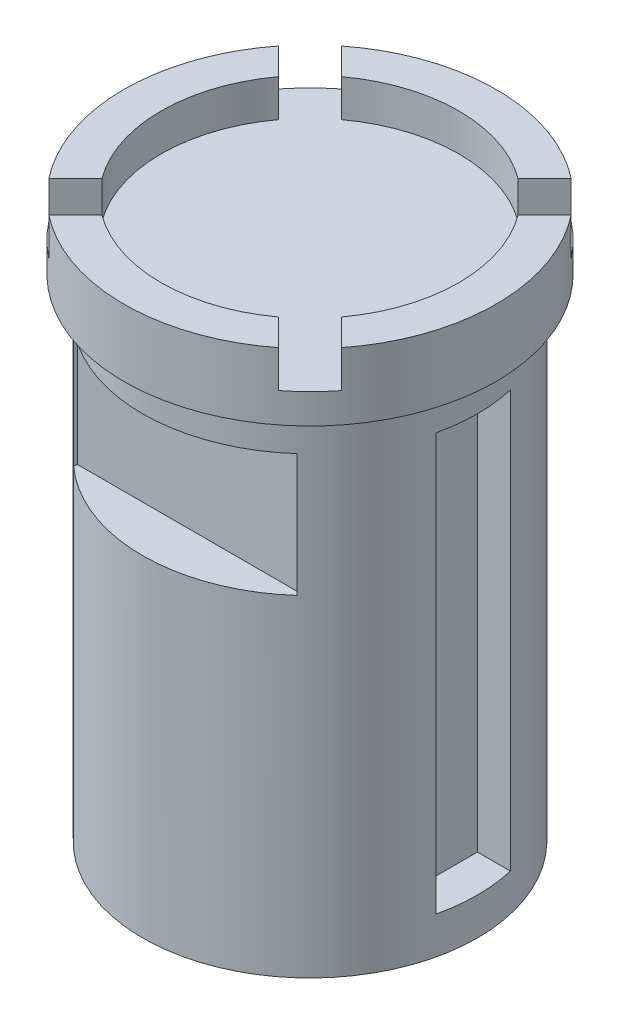
SolidWorks part; units mm, degrees
other "Satellite Body"
ref_plane "Front Plane" through (0, 0, 0) normal (0, 0, 1) x (1, 0, 0)
ref_plane "Top Plane" through (0, 0, 0) normal (0, 1, 0) x (1, 0, 0)
ref_plane "Right Plane" through (0, 0, 0) normal (1, 0, 0) x (0, 0, -1)
sketch "Body Block Sketch" plane through (0, 0, 0) normal (0, 0, 1) x (1, 0, 0)
  line L1 (0, 0) -> (400, 0)
  line L2 (0, 0) -> (0, -1400)
  line L3 (0, -1400) -> (450, -1400)
  line L6 (450, 0) -> (450, -80) construction
  line L9 (500, 0) -> (500, 100)
  line L13 (500, 100) -> (400, 100)
  line L14 (400, 0) -> (400, 100)
  line L15 (400, 0) -> (450, 0) construction
  line L16 (450, 0) -> (400, 0) construction
  line L17 (450, -80) -> (450, -1400)
  line L18 (450, -80) -> (500, -80)
  line L19 (500, 0) -> (500, -80)
  line L21 (400, 0) -> (500, 0) construction
  dimension "D1" = 1400
  dimension "D2" = 500
  dimension "D3" = 50
  dimension "D4" = 100
  dimension "D5" = 100
  dimension "D6" = 80
revolve "Body Block Revolve" add sketch "Body Block Sketch" angle 360 about L2
ref_plane "Surface Feature Start Plane" through (0, -180, 0) normal (0, -1, 0) x (-1, 0, 0)
sketch "Solar Divot Sketch" plane through (0, -180, 0) normal (0, -1, 0) x (-1, 0, 0)
  line L0 (0, 0) -> (-450, 0) construction
  line L1 (-450, 100) -> (-350, 100)
  line L2 (-450, 100) -> (-450, -100)
  line L3 (-450, -100) -> (-350, -100)
  line L4 (-350, 100) -> (-350, -100)
  line L5 (0, -926.423) -> (0, 49073.577) construction
  line L6 (350, 100) -> (350, -100)
  line L7 (450, -100) -> (350, -100)
  line L8 (450, 100) -> (450, -100)
  line L9 (450, 100) -> (350, 100)
  circle A0 centre (0, 0) radius 450 construction
  dimension "D1" = 200
  dimension "D2" = 100
extrude "Solar Divot Cut" cut sketch "Solar Divot Sketch" along normal offset from surface (1120 mm away) 100 up to face at (-450, -1400, 0)
sketch "Misc Bay Sketch" plane through (0, -180, 0) normal (0, -1, 0) x (-1, 0, 0)
  line L0 (0, 0) -> (0, 450) construction
  line L1 (-300, 450) -> (300, 450)
  line L2 (-300, 450) -> (-300, 325.4102)
  line L3 (-300, 325.4102) -> (300, 325.4102)
  line L4 (300, 450) -> (300, 325.4102)
  line L5 (-3000, 0) -> (3000, 0) construction
  line L6 (300, -450) -> (300, -325.4102)
  line L7 (-300, -325.4102) -> (300, -325.4102)
  line L8 (-300, -450) -> (300, -450)
  line L9 (-300, -450) -> (-300, -325.4102)
  circle A0 centre (0, 0) radius 450 construction
  circle A2 centre (0, 0) radius 450 construction
  point P14 (0, 0)
  point P18 (300, 335.4102)
  dimension "D1" = 600
  dimension "D2" = 10
extrude "Misc Bay Cut" cut sketch "Misc Bay Sketch" along normal blind 330
sketch "Launch Adaptor Bay Sketch" plane through (0, -1400, 0) normal (0, -1, 0) x (1, 0, 0)
  circle A2 centre (0, 0) radius 370
  circle A3 centre (0, 0) radius 370
  dimension "D1" = 80
extrude "Launch Adaptor Bay Cut" cut sketch "Launch Adaptor Bay Sketch" against normal blind 40
sketch "Gripper Gap Sketch" plane through (0, 0, 0) normal (0, 1, 0) x (1, 0, 0)
  line L0 (0, 0) -> (0, 500) construction
  line L1 (311.127, 395.9798) -> (395.9798, 311.127)
  line L2 (311.127, 395.9798) -> (-42.4264, 42.4264)
  line L3 (-42.4264, 42.4264) -> (42.4264, -42.4264)
  line L4 (395.9798, 311.127) -> (42.4264, -42.4264)
  line L5 (0, 0) -> (353.5534, 353.5534) construction
  circle A0 centre (0, 0) radius 500 construction
  dimension "D1" = 120
  dimension "D2" = 500
  dimension "D3" = 45
extrude "Gripper Gap Cut" cut sketch "Gripper Gap Sketch" along normal up to surface (100 mm away) up to face at (-400, 100, 0)
pattern_circular "Gripper Gap Cut Propagation" count 4 over 360 about axis through (0, 0, 0) along (0, -1, 0) of "Gripper Gap Cut"
ref_plane "Gripper Lip Midplane" through (0, 50, 0) normal (0, 1, 0) x (1, 0, 0)
sketch "Gripper Gap Midpoint Sketch" plane through (0, 50, 0) normal (0, 1, 0) x (1, 0, 0)
  line L0 (353.5534, 353.5534) -> (282.8427, 282.8427) construction
  line L1 (282.8427, 282.8427) -> (-282.8427, -282.8427) construction
  line L2 (0, 0) -> (353.5534, 353.5534) construction
  line L3 (-282.8427, -282.8427) -> (-353.5534, -353.5534) construction
  line L4 (0, 0) -> (-282.8427, 282.8427) construction
  line L5 (-282.8427, 282.8427) -> (-353.5534, 353.5534) construction
  line L6 (353.5534, -353.5534) -> (282.8427, -282.8427) construction
  line L7 (282.8427, -282.8427) -> (0, 0) construction
  circle A0 centre (0, 0) radius 400 construction
  circle A1 centre (0, 0) radius 500 construction
  circle A2 centre (0, 0) radius 500 construction
  arc A3 (237.2162, 322.069) -> (-237.2162, 322.069) centre (0, 0) ccw construction
  arc A4 (-393.425, 308.5722) -> (-393.425, -308.5722) centre (0, 0) ccw construction
  point P14 (318.1981, 318.1981)
  point P16 (318.1981, -318.1981)
  point P21 (0, 0)
  point P25 (318.1981, -318.1981)
  point P26 (-318.1981, -318.1981)
  point P30 (-318.1981, 318.1981)
